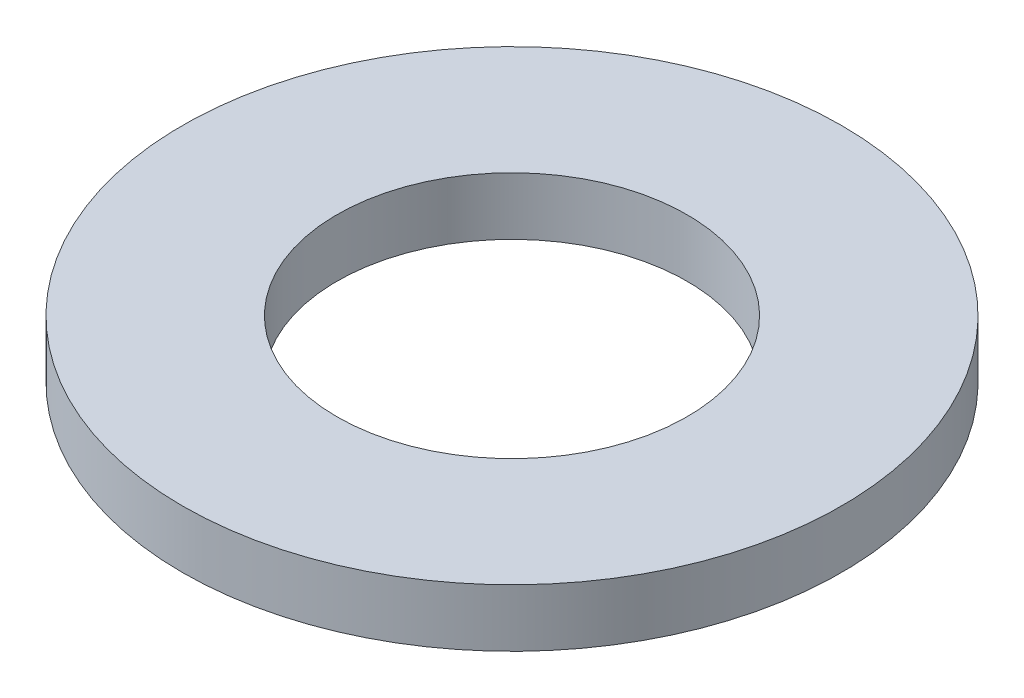
SolidWorks part; units mm, degrees
ref_plane "Front Plane" through (0, 0, 0) normal (0, 0, 1) x (1, 0, 0)
ref_plane "Top Plane" through (0, 0, 0) normal (0, 1, 0) x (1, 0, 0)
ref_plane "Right Plane" through (0, 0, 0) normal (1, 0, 0) x (0, 0, -1)
sketch "Sketch1" plane through (0, 0, 0) normal (0, 1, 0) x (1, 0, 0)
  circle A0 centre (0, 0) radius 80
  dimension "FLANGE_OD" = 160
extrude "Boss-Extrude1" add sketch "Sketch1" along normal blind 14
sketch "Sketch2" plane through (0, 0, 0) normal (0, 1, 0) x (1, 0, 0)
  circle A0 centre (0, 0) radius 42.5
  dimension "BORE_D" = 85
extrude "Cut-Extrude1" cut sketch "Sketch2" along normal through all
sketch "Sketch3" plane through (0, 14, 0) normal (0, 1, 0) x (1, 0, 0)
  circle A0 centre (0, 0) radius 25.0033 construction
  circle A1 centre (-25.0033, 0) radius 2.8577
  dimension "BOLT_D" = 5.7154
  dimension "BOLT_PCD" = 50.0066
extrude "Cut-Extrude2" cut sketch "Sketch3" against normal blind 11.4769 rebuild error yes
pattern_circular "CirPattern1" count 3 over 360 rebuild error yes
